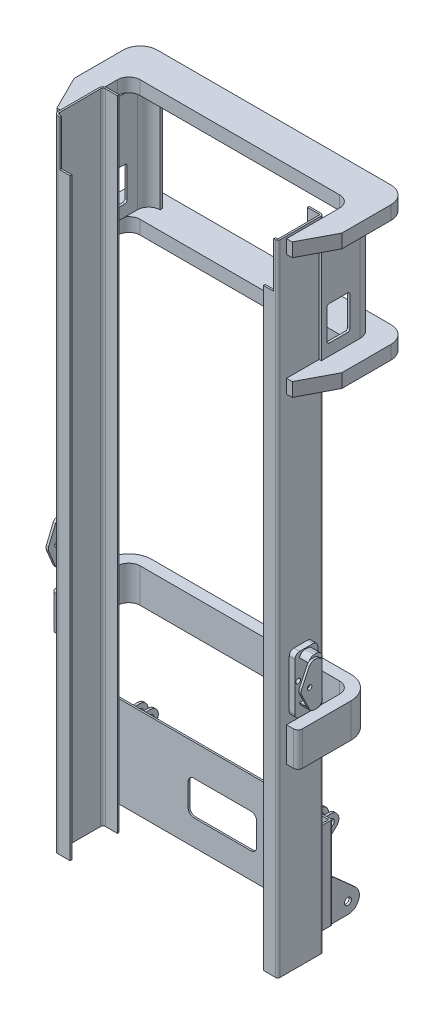
SolidWorks part; units mm, degrees
ref_plane "Front Plane" through (0, 0, 0) normal (0, 0, 1) x (1, 0, 0)
ref_plane "Top Plane" through (0, 0, 0) normal (0, 1, 0) x (1, 0, 0)
ref_plane "Right Plane" through (0, 0, 0) normal (1, 0, 0) x (0, 0, -1)
sketch "Sketch1" plane through (0, 0, 0) normal (0, 1, 0) x (1, 0, 0)
  line L0 (0, 0) -> (483, 0) construction
  line L1 (483, 90) -> (483, -90)
  line L2 (473, 100) -> (420, 100)
  line L3 (473, -100) -> (420, -100)
  arc A0 (483, -90) -> (473, -100) centre (473, -90) cw
  arc A1 (483, 90) -> (473, 100) centre (473, 90) ccw
  point P5 (483, 0)
  point P10 (483, -100)
  point P13 (483, 100)
  dimension "D4" = 10
  dimension "D1" = 483
  dimension "D2" = 200
  dimension "D3" = 63
extrude "Extrude-Thin1" add sketch "Sketch1" along normal mid plane 2800 thin thin type one direction wall 7.5
sketch "Sketch2" plane through (0, 0, 100) normal (0, 0, 1) x (1, 0, 0)
  line L1 (420, 1400) -> (465, 1400)
  line L2 (420, 1400) -> (420, 1200)
  line L3 (420, 1200) -> (465, 1200)
  line L4 (465, 1400) -> (465, 1200)
  dimension "D1" = 200
  dimension "D2" = 45
extrude "Cut-Extrude1" cut sketch "Sketch2" against normal up to next
sketch "Sketch5" plane through (0, 0, 0) normal (0, 1, 0) x (1, 0, 0)
  line L0 (0, 0) -> (-483, 0) construction
  line L1 (-420, 100) -> (-473, 100)
  line L2 (-483, 90) -> (-483, -90)
  line L3 (-473, -100) -> (-420, -100)
  arc A0 (-483, -90) -> (-473, -100) centre (-473, -90) ccw
  arc A1 (-473, 100) -> (-483, 90) centre (-473, 90) ccw
  point P9 (-483, -100)
  point P12 (-483, 100)
  dimension "D4" = 10
  dimension "D1" = 483
  dimension "D2" = 63
  dimension "D3" = 200
extrude "Extrude-Thin2" add sketch "Sketch5" along normal mid plane 2800 separate body thin thin type one direction wall 7.5
sketch "Sketch6" plane through (0, 0, 107.5) normal (0, 0, 1) x (1, 0, 0)
  line L1 (-420, 1400) -> (-465, 1400)
  line L2 (-420, 1400) -> (-420, 1200)
  line L3 (-420, 1200) -> (-465, 1200)
  line L4 (-465, 1400) -> (-465, 1200)
  dimension "D1" = 200
  dimension "D2" = 45
extrude "Cut-Extrude2" cut sketch "Sketch6" against normal up to next (7.5 mm away)
sketch "Sketch7" plane through (0, -1400, 0) normal (0, -1, 0) x (1, 0, 0)
  line L0 (473, -100) -> (473, -147.5)
  line L1 (473, -147.5) -> (-473, -147.5)
  line L2 (-473, -147.5) -> (-473, -107.5)
  arc A0 (473, -100) -> (483, -90) centre (473, -90) ccw construction
  dimension "D1" = 40
extrude "Extrude-Thin3" add sketch "Sketch7" against normal blind 400 from offset 75 separate body thin offset against normal yes thin type one direction wall 7.5
fillet "Fillet1" radius 5 2 edges at (473, -1125, -147.5) (-473, -1125, -147.5)
sketch "Sketch9" plane through (0, 0, -147.5) normal (0, 0, -1) x (-1, 0, 0)
  line L0 (-468, -925) -> (468, -925) construction
  line L1 (150, -1062.9927) -> (-150, -1062.9927)
  line L2 (150, -1062.9927) -> (150, -1212.9927)
  line L3 (150, -1212.9927) -> (-150, -1212.9927)
  line L4 (-150, -1062.9927) -> (-150, -1212.9927)
  line L5 (150, -1062.9927) -> (-150, -1212.9927) construction
  line L6 (150, -1212.9927) -> (-150, -1062.9927) construction
  point P0 (0, -1137.9927)
  point P7 (0, -925)
  dimension "D1" = 150
  dimension "D2" = 300
extrude "Cut-Extrude3" cut sketch "Sketch9" against normal up to next (7.5 mm away)
fillet "Fillet2" radius 25 4 edges at (-150, -1212.9927, -143.75) (150, -1212.9927, -143.75) (-150, -1062.9927, -143.75) (150, -1062.9927, -143.75)
sketch "Sketch11" plane through (473, 0, 0) normal (1, 0, 0) x (0, 0, -1)
  line L0 (147.5, -950) -> (192.5, -950)
  line L1 (147.5, -925) -> (147.5, -1325) construction
  line L2 (216.4057, -1010.564) -> (147.5, -1075)
  line L3 (100, -925) -> (142.5, -925) construction
  line L4 (147.5, -950) -> (147.5, -1075)
  arc A0 (192.5, -950) -> (216.4057, -1010.564) centre (192.5, -985) cw
  circle A1 centre (192.5, -985) radius 15
  dimension "D3" = 35
  dimension "D5" = 30
  dimension "D1" = 45
  dimension "D2" = 25
  dimension "D4" = 125
extrude "Boss-Extrude1" add sketch "Sketch11" against normal blind 10 from offset 50 offset against normal yes
pattern_linear "LPattern1" count 2 spacing 45 along (-1, 0, 0) of "Boss-Extrude1"
mirror "Mirror11" about plane through (0, 0, 0) normal (1, 0, 0) of "LPattern1", "Boss-Extrude1"
sketch "Sketch12" plane through (473, 0, 0) normal (1, 0, 0) x (0, 0, -1)
  line L0 (147.5, -1325) -> (222.5, -1325)
  line L1 (255.787, -1237.6908) -> (157.5, -1150)
  line L2 (157.5, -1150) -> (147.5, -1150)
  line L3 (147.5, -925) -> (147.5, -1325) construction
  line L4 (147.5, -1150) -> (147.5, -1325)
  arc A0 (222.5, -1325) -> (255.787, -1237.6908) centre (222.5, -1275) ccw
  circle A1 centre (222.5, -1275) radius 15
  dimension "D4" = 50
  dimension "D5" = 30
  dimension "D1" = 75
  dimension "D2" = 175
  dimension "D3" = 10
extrude "Boss-Extrude2" add sketch "Sketch12" against normal blind 10 from offset 5 offset against normal yes
mirror "Mirror13" about plane through (0, 0, 0) normal (1, 0, 0) of "Boss-Extrude2"
sketch "Sketch13" plane through (0, 1400, 0) normal (0, 1, 0) x (1, 0, 0)
  line L0 (-490.5, -69.5) -> (-515.5, -69.5)
  line L1 (-490.5, 90) -> (-490.5, -90) construction
  line L2 (-515.5, -69.5) -> (-590.5, 80.5)
  line L3 (-590.5, 80.5) -> (-590.5, 295.5)
  line L5 (0, 459.9733) -> (0, -89.7014) construction
  line L6 (0, 220.5) -> (-440.5, 220.5)
  line L7 (-490.5, 170.5) -> (-490.5, -69.5)
  line L8 (-465, -107.5) -> (-420, -107.5) construction
  line L10 (508.2118, -62) -> (583.212, 80.5)
  line L13 (483.2118, -62) -> (483.2121, 170.4999)
  line L17 (583.212, 80.5) -> (583.2123, 295.4773)
  line L19 (-490.5, -139.5862) -> (490.5, -139.5862)
  line L20 (483.2118, -62) -> (508.2118, -62)
  line L21 (420, -100) -> (465, -100) construction
  line L22 (0, 220.5) -> (433.2121, 220.5)
  line L23 (-515.5, 370.5) -> (507.9837, 370.4771)
  arc A0 (-440.5, 220.5) -> (-490.5, 170.5) centre (-440.5, 170.5) ccw
  arc A1 (-590.5, 295.5) -> (-515.5, 370.5) centre (-515.5, 295.5) cw
  arc A2 (583.2123, 295.4773) -> (507.9837, 370.4771) centre (508.2123, 295.4774) ccw
  arc A3 (483.2121, 170.4999) -> (433.2121, 220.5) centre (433.2121, 170.5) ccw
  point P7 (0, -139.5862)
  point P10 (0, 370.5)
  point P27 (0, 220.5)
  point P33 (583.2123, 370.5)
  dimension "D7" = 50
  dimension "D8" = 75
  dimension "D13" = 75
  dimension "D14" = 50
  dimension "D1" = 25
  dimension "D2" = 150
  dimension "D3" = 100
  dimension "D6" = 38
  dimension "D9" = 25
  dimension "D10" = 38
  dimension "D11" = 100
  dimension "D12" = 290
extrude "Boss-Extrude3" add sketch "Sketch13" along normal blind 60 from offset 600 contours L5 L23 A1 L3 L2 L0 L7 A0 L6 | L23 L5 L22 A3 L13 L20 L10 L17 A2 region at (-343.3737, 1400, -253.0392) region at (338.6894, 1400, -253.8454) offset against normal yes
pattern_linear "LPattern2" count 2 spacing 530 along (0, 1, 0) of "Boss-Extrude3"
sketch "Sketch14" plane through (0, 860, 0) normal (0, 1, 0) x (1, 0, 0)
  line L0 (483, 80.5) -> (483, 250)
  line L1 (420, 100) -> (473, 100) construction
  line L4 (433.2121, 220.5) -> (-440.5, 220.5) construction
  arc A0 (483, 250) -> (433, 300) centre (433, 250) ccw
  dimension "D1" = 50
  dimension "D2" = 150
  dimension "D3" = 140
extrude "Extrude-Thin4" add sketch "Sketch14" along normal blind 470 thin thin type one direction wall 10
sketch "Sketch15" plane through (493, 0, 0) normal (1, 0, 0) x (0, 0, -1)
  line L0 (80.5, 860) -> (295.4773, 860) construction
  line L1 (195.5, 910) -> (115.5, 910)
  line L2 (205.5, 920) -> (205.5, 1050)
  line L3 (195.5, 1060) -> (115.5, 1060)
  line L4 (105.5, 920) -> (105.5, 1050)
  line L5 (205.5, 910) -> (105.5, 1060) construction
  line L6 (205.5, 1060) -> (105.5, 910) construction
  line L7 (80.5, 1330) -> (80.5, 860) construction
  arc A0 (115.5, 910) -> (105.5, 920) centre (115.5, 920) cw
  arc A1 (195.5, 910) -> (205.5, 920) centre (195.5, 920) ccw
  arc A2 (205.5, 1050) -> (195.5, 1060) centre (195.5, 1050) ccw
  arc A3 (115.5, 1060) -> (105.5, 1050) centre (115.5, 1050) ccw
  point P0 (155.5, 985)
  dimension "D5" = 10
  dimension "D1" = 100
  dimension "D2" = 150
  dimension "D3" = 50
  dimension "D4" = 25
extrude "Cut-Extrude4" cut sketch "Sketch15" against normal up to next (10 mm away)
mirror "Mirror14" about plane through (0, 0, 0) normal (1, 0, 0) of "Cut-Extrude4", "Extrude-Thin4"
sketch "Sketch16" plane through (-490.5, 0, 0) normal (-1, 0, 0) x (0, 0, 1)
  line L0 (-90, -1400) -> (90, -1400) construction
  line L1 (30, -180) -> (-30, -180)
  line L2 (50, -200) -> (50, -410)
  line L3 (30, -430) -> (-30, -430)
  line L4 (-50, -200) -> (-50, -410)
  line L5 (50, -180) -> (-50, -430) construction
  line L6 (50, -430) -> (-50, -180) construction
  arc A0 (-30, -430) -> (-50, -410) centre (-30, -410) cw
  arc A1 (50, -410) -> (30, -430) centre (30, -410) cw
  arc A2 (30, -180) -> (50, -200) centre (30, -200) cw
  arc A3 (-30, -180) -> (-50, -200) centre (-30, -200) ccw
  point P0 (0, -305)
  dimension "D4" = 20
  dimension "D1" = 250
  dimension "D2" = 100
  dimension "D3" = 1220
extrude "Boss-Extrude4" add sketch "Sketch16" along normal blind 25
sketch "Sketch17" plane through (-515.5, 0, 0) normal (-1, 0, 0) x (0, 0, 1)
  line L0 (30, -200) -> (-30, -200)
  line L1 (-30, -200) -> (-30, -410)
  line L2 (-30, -410) -> (30, -410)
  line L3 (30, -410) -> (30, -200)
  line L4 (-30, -430) -> (30, -430)
  line L5 (50, -410) -> (50, -200)
  line L6 (30, -180) -> (-30, -180)
  line L7 (-50, -200) -> (-50, -410)
  line L8 (-30, -430) -> (30, -430)
  line L9 (50, -410) -> (50, -200)
  line L10 (30, -180) -> (-30, -180)
  line L11 (-50, -200) -> (-50, -410)
  arc A0 (-30, -200) -> (-30, -200) centre (-30, -200) ccw
  arc A1 (-30, -410) -> (-30, -410) centre (-30, -410) ccw
  arc A2 (30, -410) -> (30, -410) centre (30, -410) ccw
  arc A3 (30, -200) -> (30, -200) centre (30, -200) ccw
  arc A4 (-50, -410) -> (-30, -430) centre (-30, -410) ccw
  arc A5 (30, -430) -> (50, -410) centre (30, -410) ccw
  arc A6 (50, -200) -> (30, -180) centre (30, -200) ccw
  arc A7 (-30, -180) -> (-50, -200) centre (-30, -200) ccw
  arc A8 (-50, -410) -> (-30, -430) centre (-30, -410) ccw
  arc A9 (30, -430) -> (50, -410) centre (30, -410) ccw
  arc A10 (50, -200) -> (30, -180) centre (30, -200) ccw
  arc A11 (-30, -180) -> (-50, -200) centre (-30, -200) ccw
  dimension "D1" = 0
  dimension "D2" = 20
extrude "Boss-Extrude5" add sketch "Sketch17" along normal blind 40 contours L2 L3 L0 L1 region at (-515.5, -305, 0)
sketch "Sketch18" plane through (-555.5, 0, 0) normal (-1, 0, 0) x (0, 0, 1)
  line L4 (10, -220) -> (30, -220)
  line L5 (30, -410) -> (30, -200) construction
  line L6 (30, -220) -> (30, -390)
  line L7 (30, -410) -> (30, -200) construction
  line L8 (-10, -390) -> (10, -390)
  line L9 (10, -390) -> (10, -220)
  line L10 (10, -220) -> (-10, -220)
  line L11 (-10, -220) -> (-10, -390)
  line L12 (-10, -390) -> (10, -390)
  line L13 (10, -390) -> (10, -220)
  line L14 (10, -220) -> (-10, -220)
  line L15 (-10, -220) -> (-10, -390)
  line L16 (30, -390) -> (10, -390)
  line M6 (30, -410) -> (30, -200)
  dimension "D1" = 20
extrude "Cut-Extrude5" cut sketch "Sketch18" against normal blind 40 contours L14 L15 L12 L13 | L16 L4 L13 M6 region at (-555.5, -305, 20) region at (-555.5, -305, 0)
sketch "Sketch20" plane through (-555.5, 0, 0) normal (-1, 0, 0) x (0, 0, 1)
  line L0 (-21.7221, -210) -> (30, -210)
  line L1 (30, -220) -> (30, -200) construction
  line L2 (30, -210) -> (69.4984, -305)
  line L3 (69.4984, -305) -> (30, -400)
  line L4 (30, -410) -> (30, -390) construction
  line L5 (30, -400) -> (-21.7221, -400)
  line L6 (-21.7221, -400) -> (-21.7221, -210)
extrude "Boss-Extrude6" add sketch "Sketch20" along normal blind 10
sketch "Sketch21" plane through (-565.5, 0, 0) normal (-1, 0, 0) x (0, 0, 1)
  circle A0 centre (29.4984, -305) radius 10
  dimension "D1" = 20
  dimension "D2" = 40
extrude "Cut-Extrude6" cut sketch "Sketch21" against normal up to surface (75 mm away) up to face at (-490.5, 730, -5.25)
fillet "Fillet3" radius 25 5 edges at (-535.5, -200, -30) (-535.5, -410, -30) (-535.5, -410, 30) (-560.5, -305, 69.4984) (-535.5, -200, 30)
fillet "Fillet4" radius 25 4 edges at (-560.5, -400, 30) (-560.5, -400, -21.7221) (-560.5, -210, -21.7221) (-560.5, -210, 30)
sketch "Sketch26" plane through (483, 0, 0) normal (1, 0, 0) x (0, 0, -1)
  line L0 (90, -1400) -> (-90, -1400) construction
  line L1 (30, -180) -> (-30, -180)
  line L2 (50, -200) -> (50, -410)
  line L3 (30, -430) -> (-30, -430)
  line L4 (-50, -200) -> (-50, -410)
  arc A0 (50, -410) -> (30, -430) centre (30, -410) cw
  arc A1 (-30, -430) -> (-50, -410) centre (-30, -410) cw
  arc A2 (30, -180) -> (50, -200) centre (30, -200) cw
  arc A3 (-30, -180) -> (-50, -200) centre (-30, -200) ccw
  point P4 (0, -180)
  point P10 (-50, -430)
  point P13 (50, -180)
  point P16 (-50, -180)
  dimension "D3" = 20
  dimension "D1" = 250
  dimension "D2" = 100
  dimension "D4" = 1220
extrude "Boss-Extrude7" add sketch "Sketch26" along normal blind 25
sketch "Sketch27" plane through (508, 0, 0) normal (1, 0, 0) x (0, 0, -1)
  line L0 (30, -184.4711) -> (-30, -184.4711)
  line L1 (-30, -184.4711) -> (-30, -394.4711)
  line L2 (-30, -394.4711) -> (30, -394.4711)
  line L3 (30, -394.4711) -> (30, -184.4711)
  line L8 (50, -394.4711) -> (50, -184.4711)
  line L9 (30, -164.4711) -> (-30, -164.4711)
  line L10 (-50, -184.4711) -> (-50, -394.4711)
  line L11 (-30, -414.4711) -> (30, -414.4711)
  arc A8 (30, -414.4711) -> (50, -394.4711) centre (30, -394.4711) ccw
  arc A9 (50, -184.4711) -> (30, -164.4711) centre (30, -184.4711) ccw
  arc A10 (-30, -164.4711) -> (-50, -184.4711) centre (-30, -184.4711) ccw
  arc A11 (-50, -394.4711) -> (-30, -414.4711) centre (-30, -394.4711) ccw
extrude "Boss-Extrude8" add sketch "Sketch27" along normal blind 40 contours L2 L3 L0 L1 region at (508, -289.4711, 0)
sketch "Sketch28" plane through (548, 0, 0) normal (1, 0, 0) x (0, 0, -1)
  line L4 (-10, -204.4711) -> (-30, -204.4711)
  line L6 (-30, -184.4711) -> (-30, -394.4711) construction
  line L7 (-30, -204.4711) -> (-30, -374.4711)
  line L8 (-10, -374.4711) -> (10, -374.4711)
  line L9 (10, -374.4711) -> (10, -204.4711)
  line L10 (10, -204.4711) -> (-10, -204.4711)
  line L11 (-10, -204.4711) -> (-10, -374.4711)
  line L12 (-10, -374.4711) -> (10, -374.4711)
  line L13 (10, -374.4711) -> (10, -204.4711)
  line L14 (10, -204.4711) -> (-10, -204.4711)
  line L15 (-10, -204.4711) -> (-10, -374.4711)
  line L16 (-30, -374.4711) -> (-10, -374.4711)
  line M8 (-30, -184.4711) -> (-30, -394.4711)
  dimension "D1" = 20
extrude "Cut-Extrude8" cut sketch "Sketch28" against normal blind 40 contours L16 L15 L4 M8 | L14 L15 L12 L13 region at (548, -289.4711, 20) region at (548, -289.4711, 0)
sketch "Sketch30" plane through (548, 0, 0) normal (1, 0, 0) x (0, 0, -1)
  line L0 (19.346, -194.4711) -> (-30, -194.4711)
  line L1 (-30, -184.4711) -> (-30, -204.4711) construction
  line L2 (-30, -194.4711) -> (-75.7773, -289.4711)
  line L3 (-75.7773, -289.4711) -> (-30, -384.4711)
  line L4 (-30, -374.4711) -> (-30, -394.4711) construction
  line L5 (-30, -384.4711) -> (19.346, -384.4711)
  line L6 (19.346, -384.4711) -> (19.346, -194.4711)
extrude "Boss-Extrude10" add sketch "Sketch30" along normal blind 10
sketch "Sketch31" plane through (558, 0, 0) normal (1, 0, 0) x (0, 0, -1)
  circle A0 centre (-35.7773, -289.4711) radius 10
  dimension "D1" = 20
  dimension "D2" = 40
extrude "Cut-Extrude9" cut sketch "Sketch31" against normal up to surface (75 mm away) up to face at (483, 547.5, -42.625)
fillet "Fillet5" radius 25 5 edges at (528, -394.4711, -30) (528, -184.4711, -30) (528, -184.4711, 30) (528, -394.4711, 30) (553, -289.4711, 75.7773)
fillet "Fillet6" radius 25 4 edges at (553, -384.4711, 30) (553, -384.4711, -19.346) (553, -194.4711, -19.346) (553, -194.4711, 30)
sketch "Sketch33" plane through (0, -430, 0) normal (0, -1, 0) x (1, 0, 0)
  line L0 (-490.5, -90) -> (-490.5, 69.5) construction
  line L1 (-490.5, -170.5) -> (-490.5, -90) construction
  line L2 (433.2121, -220.5) -> (-440.5, -220.5) construction
  line L3 (483.2118, 62) -> (483.2121, -170.4999) construction
  line L4 (483, -90) -> (483, 90) construction
  line L5 (-490.5, -90) -> (-490.5, 69.5)
  line L6 (-490.5, -170.5) -> (-490.5, -90)
  line L7 (433.2121, -220.5) -> (-440.5, -220.5)
  line L8 (483.2118, 62) -> (483.2121, -170.4999)
  line L9 (483, -90) -> (483, 90)
  line L10 (533.2118, 62.0001) -> (533.2121, -170.4999)
  line L11 (433.2121, -270.5) -> (-440.5, -270.5)
  line L12 (-540.5, -170.5) -> (-540.5, -90)
  line L13 (-540.5, -90) -> (-540.5, 69.5)
  line L14 (-540.5, 69.5) -> (-490.5, 69.5)
  line L15 (533.2118, 62.0001) -> (483.2118, 62)
  arc A0 (-490.5, -170.5) -> (-440.5, -220.5) centre (-440.5, -170.5) ccw construction
  arc A1 (433.2121, -220.5) -> (483.2121, -170.4999) centre (433.2121, -170.5) ccw construction
  arc A2 (-490.5, -170.5) -> (-440.5, -220.5) centre (-440.5, -170.5) ccw
  arc A3 (433.2121, -220.5) -> (483.2121, -170.4999) centre (433.2121, -170.5) ccw
  arc A4 (433.2121, -270.5) -> (533.2121, -170.4999) centre (433.2121, -170.5) ccw
  arc A5 (-540.5, -170.5) -> (-440.5, -270.5) centre (-440.5, -170.5) ccw
  dimension "D1" = 50
extrude "Boss-Extrude14" add sketch "Sketch33" along normal blind 150 from offset 25 contours L11 A5 L12 L13 L14 L5 L6 A2 L7 A3 L8 L15 L10 A4
fillet "Fillet7" radius 20 2 edges at (-540.5, -530, 69.5) (533.2118, -530, 62.0001)
sketch "Sketch34" plane through (0, 0, -30) normal (0, 0, -1) x (-1, 0, 0)
  line L0 (-548, -369.4711) -> (-508, -369.4711) construction
  line L1 (-508, -369.4711) -> (-508, -209.4711) construction
  line L2 (-508, -209.4711) -> (-548, -209.4711) construction
  line L3 (-548, -369.4711) -> (-548, -209.4711) construction
  line L4 (-548, -369.4711) -> (-508, -369.4711)
  line L5 (-508, -369.4711) -> (-508, -209.4711)
  line L6 (-508, -209.4711) -> (-548, -209.4711)
  line L7 (-548, -369.4711) -> (-548, -209.4711)
extrude "Cut-Extrude10" cut sketch "Sketch34" against normal blind 70
sketch "Sketch35" plane through (0, 0, -30) normal (0, 0, -1) x (-1, 0, 0)
  line L4 (555.5, -385) -> (555.5, -225)
  line L5 (555.5, -225) -> (515.5, -225)
  line L6 (515.5, -225) -> (515.5, -385)
  line L7 (515.5, -385) -> (555.5, -385)
  line L8 (555.5, -385) -> (555.5, -225)
  line L9 (555.5, -225) -> (515.5, -225)
  line L10 (515.5, -225) -> (515.5, -385)
  line L11 (515.5, -385) -> (555.5, -385)
  dimension "D1" = 0
extrude "Cut-Extrude11" cut sketch "Sketch35" against normal blind 90
